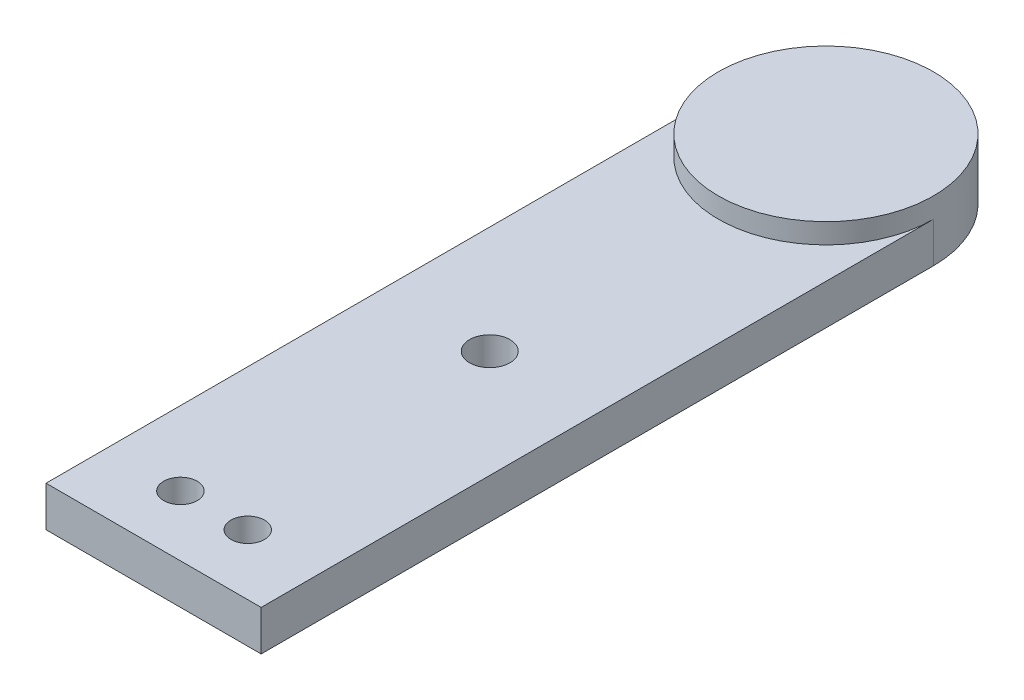
SolidWorks part; units mm, degrees
ref_plane "Plano frontal" through (0, 0, 0) normal (0, 0, 1) x (1, 0, 0)
ref_plane "Plano superior" through (0, 0, 0) normal (0, 1, 0) x (1, 0, 0)
ref_plane "Plano direito" through (0, 0, 0) normal (1, 0, 0) x (0, 0, -1)
sketch "Sketch1" plane through (0, 0, 0) normal (0, 1, 0) x (1, 0, 0)
  circle A0 centre (0, 0) radius 8
  dimension "D1" = 16
extrude "Boss-Extrude1" add sketch "Sketch1" against normal blind 1.5 and the other way blind 3
sketch "Sketch2" plane through (0, 0, 0) normal (0, 1, 0) x (1, 0, 0)
  line L1 (-8, 0) -> (8, 0)
  line L2 (-8, 0) -> (-8, -50)
  line L3 (-8, -50) -> (8, -50)
  line L4 (8, 0) -> (8, -50)
  circle A1 centre (0, 0) radius 8 construction
  dimension "D1" = 50
extrude "Boss-Extrude2" add sketch "Sketch2" along normal mid plane 3
sketch "Sketch3" plane through (0, -1.5, 0) normal (0, -1, 0) x (-1, 0, 0)
  line L1 (8, -50) -> (-8, -50) construction
  circle A0 centre (2.5031, -45.5) radius 1.25
  circle A1 centre (-2.5031, -45.5) radius 1.25
  dimension "D4" = 2.5
  dimension "D5" = 2.5
  dimension "D1" = 2.5031
  dimension "D2" = 2.5031
  dimension "D3" = 4.5
extrude "Cut-Extrude1" cut sketch "Sketch3" against normal up to next
sketch "Sketch4" plane through (0, -1.5, 0) normal (0, -1, 0) x (-1, 0, 0)
  line L0 (-3.3, 0) -> (3.3, 0)
  circle A0 centre (0, 0) radius 3.3
  dimension "D1" = 6.6
revolve "Cut-Revolve21" cut sketch "Sketch4" angle 360 about L0 region at (0, -1.5, 1.4006)
sketch "Sketch5" plane through (0, 1.5, 0) normal (0, 1, 0) x (1, 0, 0)
  line L3 (-8, 0) -> (-8, -50)
  line L4 (-8, -50) -> (8, -50)
  line L5 (8, -50) -> (8, 0)
  line L6 (-8, 0) -> (-8, -50)
  line L7 (-8, -50) -> (8, -50)
  line L8 (8, -50) -> (8, 0)
  circle A0 centre (0, -25) radius 1.5
  arc A1 (-8, 0) -> (8, 0) centre (0, 0) ccw
  arc A2 (-8, 0) -> (8, 0) centre (0, 0) ccw
  point P7 (0, 0)
  dimension "D4" = 3
  dimension "D2" = 50
  dimension "D3" = 25
extrude "Cut-Extrude3" cut sketch "Sketch5" against normal up to next contours A0
equation "\"D2@Sketch3\"=\"D1@Sketch3\""
equation "\"D5@Sketch3\"=\"D4@Sketch3\""
equation "\"D3@Sketch5\"=\"D2@Sketch5\"/2"
